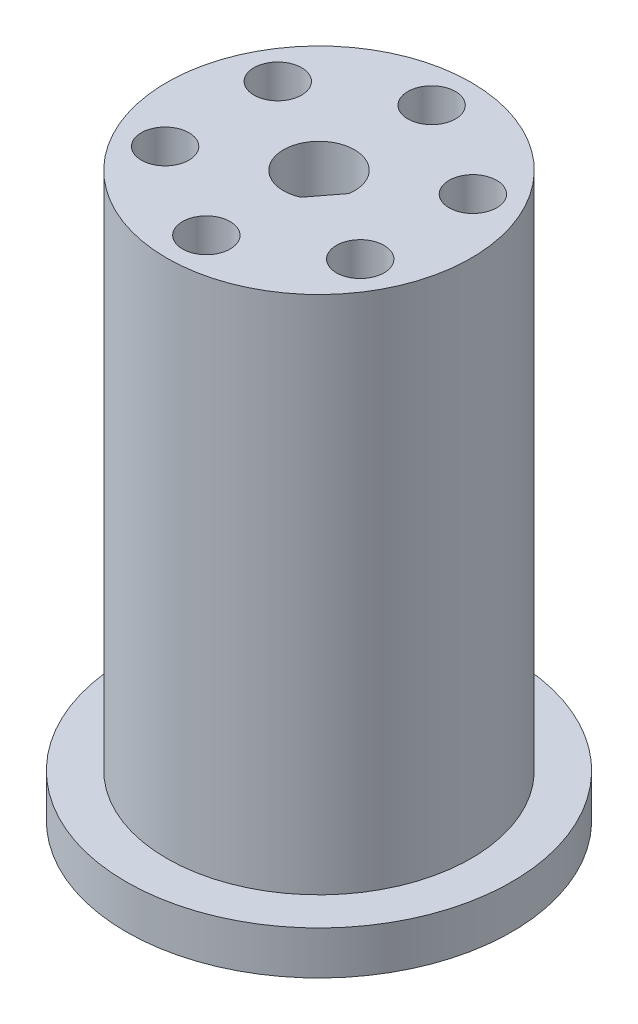
SolidWorks part; units mm, degrees
ref_plane "Front Plane" through (0, 0, 0) normal (0, 0, 1) x (1, 0, 0)
ref_plane "Top Plane" through (0, 0, 0) normal (0, 1, 0) x (1, 0, 0)
ref_plane "Right Plane" through (0, 0, 0) normal (1, 0, 0) x (0, 0, -1)
sketch "Sketch2" plane through (0, 0, 0) normal (0, 1, 0) x (1, 0, 0)
  circle A0 centre (0, 0) radius 22.25
extrude "Boss-Extrude1" add sketch "Sketch2" along normal blind 5
sketch "Sketch3" plane through (0, 5, 0) normal (0, 1, 0) x (1, 0, 0)
  circle A0 centre (0, 0) radius 17.567
extrude "Boss-Extrude2" add sketch "Sketch3" along normal blind 60
sketch "Sketch4" plane through (0, 65, 0) normal (0, 1, 0) x (1, 0, 0)
  line L8 (4.0552, -0.6042) -> (1.7013, -3.6797)
  line L9 (1.6425, -3.7566) -> (1.7013, -3.6797)
  circle A0 centre (0, 13) radius 2.75
  circle A2 centre (-11.2583, 6.5) radius 2.75
  circle A3 centre (-11.2583, -6.5) radius 2.75
  circle A4 centre (0, -13) radius 2.75
  circle A5 centre (11.2583, -6.5) radius 2.75
  circle A6 centre (11.2583, 6.5) radius 2.75
  arc A10 (4.0552, -0.6042) -> (1.6425, -3.7566) centre (0, 0) ccw
  point P17 (0, 0)
  dimension "D2" = 13
  dimension "D1" = 3.873
extrude "Cut-Extrude1" cut sketch "Sketch4" against normal blind 73
sketch "Sketch5" plane through (0, 0, 0) normal (0, -1, 0) x (1, 0, 0)
  circle A0 centre (0, 13) radius 4.5
  circle A1 centre (11.2583, 6.5) radius 4.5
  circle A2 centre (11.2583, -6.5) radius 4.5
  circle A3 centre (0, -13) radius 4.5
  circle A4 centre (-11.2583, -6.5) radius 4.5
  circle A5 centre (-11.2583, 6.5) radius 4.5
extrude "Cut-Extrude2" cut sketch "Sketch5" against normal blind 5.5
